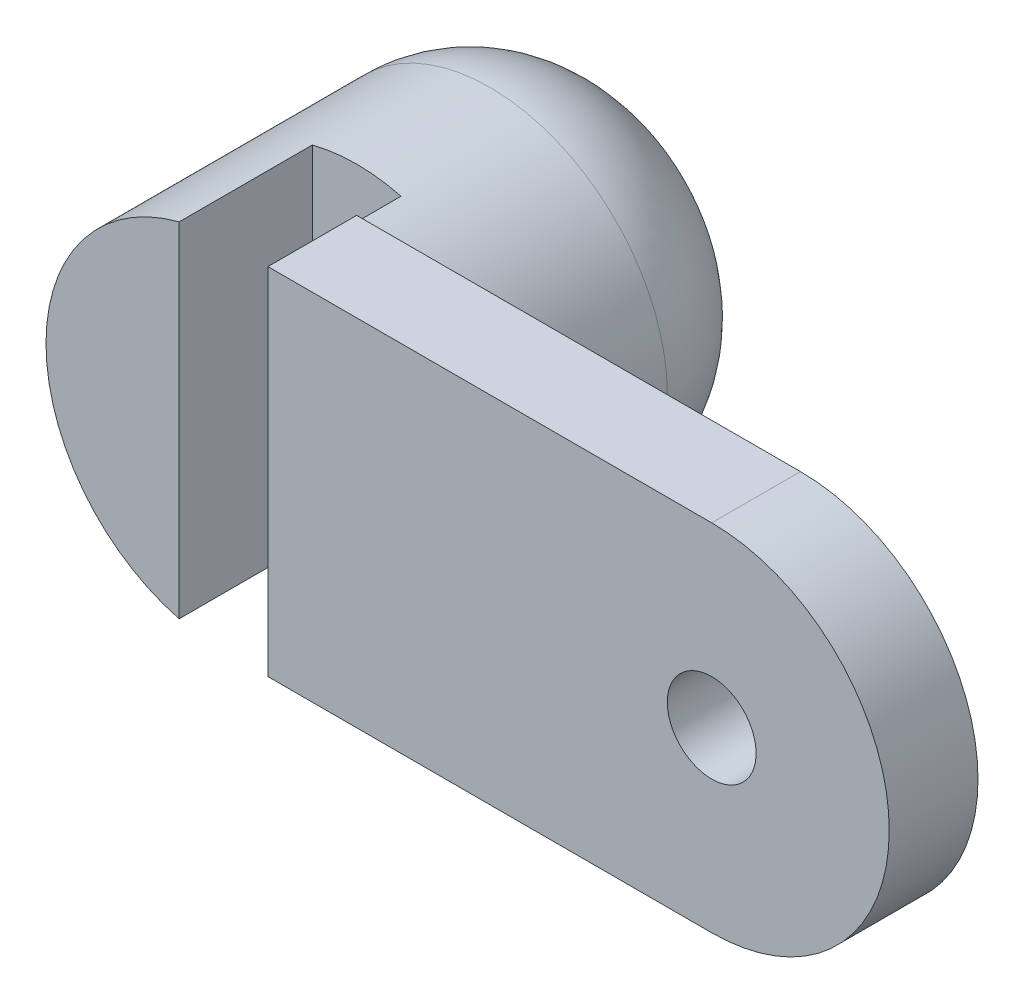
SolidWorks part; units mm, degrees
ref_plane "前视基准面" through (0, 0, 0) normal (0, 0, 1) x (1, 0, 0)
ref_plane "上视基准面" through (0, 0, 0) normal (0, 1, 0) x (1, 0, 0)
ref_plane "右视基准面" through (0, 0, 0) normal (1, 0, 0) x (0, 0, -1)
other "Configuration Table"
sketch "草图1" plane through (0, 0, 0) normal (0, 0, 1) x (1, 0, 0)
  circle A0 centre (0, 0) radius 2
  circle A1 centre (0, 0) radius 0.5
  dimension "D1" = 4
  dimension "D2" = 1
extrude "凸台-拉伸1" add sketch "草图1" along normal blind 4.5
fillet "圆角2" radius 1.5 1 edges at (2, 0, 0)
sketch "草图3" plane through (0, 0, 0) normal (0, 1, 0) x (1, 0, 0)
  line L0 (0, 0) -> (0, -3.5) construction
  line L1 (0, -3.5) -> (0, -4.5)
  line L2 (0, -3.5) -> (5.5, -3.5)
  line L3 (5.5, -3.5) -> (5.5, -4.5)
  line L4 (0, -4.5) -> (5.5, -4.5)
  dimension "D1" = 3.5
  dimension "D2" = 1
  dimension "D3" = 5.5
  dimension "D4" = 1
extrude "凸台-拉伸2" add sketch "草图3" along normal mid plane 4
sketch "草图4" plane through (0, 0, 3.5) normal (0, 0, -1) x (-1, 0, 0)
  line L0 (-5.5, 2) -> (-5.5, -2) construction
  circle A0 centre (-5.5, 0) radius 2
  circle A1 centre (-5.5, 0) radius 0.5
  dimension "D1" = 1
extrude "凸台-拉伸3" add sketch "草图4" against normal blind 1
sketch "草图5" plane through (0, 0, 3.5) normal (0, 0, -1) x (-1, 0, 0)
  line L0 (-5.5, 0.5) -> (-5.5, -0.5) construction
  circle A0 centre (-5.5, 0) radius 0.5
  dimension "D1" = 1
extrude "切除-拉伸2" cut sketch "草图5" against normal blind 4
sketch "草图6" plane through (0, 0, 4.5) normal (0, 0, 1) x (1, 0, 0)
  circle A0 centre (0, 0) radius 0.5
  dimension "D1" = 1
extrude "切除-拉伸3" cut sketch "草图6" against normal through all
sketch "草图2" plane through (0, 0, 4.5) normal (0, 0, 1) x (1, 0, 0)
  line L1 (-0.5, -2.0824) -> (0.5, -2.0824)
  line L2 (-0.5, -2.0824) -> (-0.5, 2.0824)
  line L3 (-0.5, 2.0824) -> (0.5, 2.0824)
  line L4 (0.5, -2.0824) -> (0.5, 2.0824)
  line L5 (-0.5, -2.0824) -> (0.5, 2.0824) construction
  line L6 (-0.5, 2.0824) -> (0.5, -2.0824) construction
  point P0 (0, 0)
  dimension "D1" = 1
extrude "切除-拉伸1" cut sketch "草图2" against normal blind 1.5
